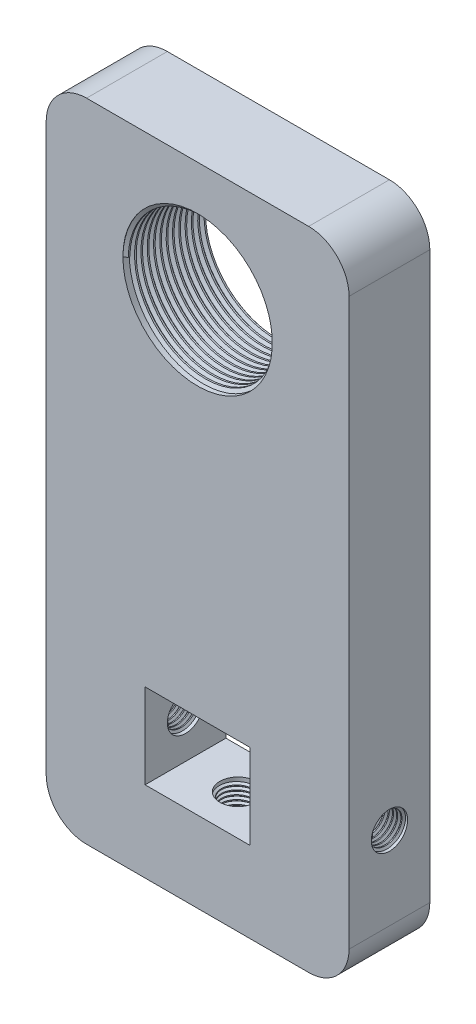
SolidWorks part; units mm, degrees
ref_plane "Front Plane" through (0, 0, 0) normal (0, 0, 1) x (1, 0, 0)
ref_plane "Top Plane" through (0, 0, 0) normal (0, 1, 0) x (1, 0, 0)
ref_plane "Right Plane" through (0, 0, 0) normal (1, 0, 0) x (0, 0, -1)
sketch "Sketch1" plane through (0, 0, 0) normal (0, 0, 1) x (1, 0, 0)
  line L2 (0, 0) -> (0, 66.04)
  line L3 (5.08, 71.12) -> (33.02, 71.12)
  line L4 (38.1, 0) -> (38.1, 66.04)
  line L5 (12.446, 0) -> (12.446, 10.668)
  line L6 (12.446, 10.668) -> (25.654, 10.668)
  line L7 (25.654, 10.668) -> (25.654, 0)
  line L11 (0, 0) -> (0, -5.08)
  line L12 (5.08, -10.16) -> (33.02, -10.16)
  line L13 (38.1, -5.08) -> (38.1, 0)
  line L14 (12.446, 0) -> (25.654, 0)
  line L15 (19.05, 71.12) -> (19.05, 56.134) construction
  line L16 (19.05, 56.134) -> (19.05, 25.654) construction
  line L17 (19.05, 10.668) -> (19.05, 25.654) construction
  line L18 (19.05, 0) -> (19.05, -10.16) construction
  line L19 (0, 10.668) -> (38.1, 10.668) construction
  arc A3 (0, -5.08) -> (5.08, -10.16) centre (5.08, -5.08) ccw
  arc A4 (33.02, -10.16) -> (38.1, -5.08) centre (33.02, -5.08) ccw
  arc A5 (33.02, 71.12) -> (38.1, 66.04) centre (33.02, 66.04) cw
  arc A6 (0, 66.04) -> (5.08, 71.12) centre (5.08, 66.04) cw
  circle A8 centre (19.05, 56.134) radius 9.398
  point P16 (19.05, 71.12)
  point P27 (0, 71.12)
  dimension "D5" = 18.796
  dimension "D7" = 5.08
  dimension "D1" = 13.208
  dimension "D2" = 71.12
  dimension "D3" = 10.668
  dimension "D4" = 10.16
  dimension "D8" = 38.1
extrude "Boss-Extrude2" add sketch "Sketch1" along normal blind 10.16
sketch "Sketch4" plane through (0, 0, 0) normal (-1, 0, 0) x (0, 0, 1)
  circle A0 centre (5.08, 5.334) radius 2.286
  dimension "D1" = 4.572
  dimension "D2" = 5.334
extrude "Cut-Extrude1" cut sketch "Sketch4" against normal blind 38.1
sketch "Sketch6" plane through (0, -10.16, 0) normal (0, -1, 0) x (1, 0, 0)
  line L0 (19.05, 5.08) -> (19.05, 10.16) construction
  line L1 (5.08, 10.16) -> (33.02, 10.16) construction
  line L2 (19.05, 5.08) -> (33.02, 5.08) construction
  line L3 (33.02, 10.16) -> (33.02, 0) construction
  circle A0 centre (19.05, 5.08) radius 2.286
  dimension "D1" = 4.572
extrude "Cut-Extrude2" cut sketch "Sketch6" against normal blind 10.16
thread "Thread1" pitch 0.7937 method extrude profile "Thread Profile1" start angle 0, offset 0, length 9.652, pitch 0.7937, diameter 18.796
ref_plane "Plane1" through (9.652, 56.134, 10.16) normal (0, -1, 0) x (-1, 0, 0)
sketch "Thread Profile1" plane through (9.652, 56.134, 10.16) normal (0, -1, 0) x (-1, 0, 0)
  line L0 (0, 0) -> (0, 0.7937) construction
  line L11 (0, 0) -> (0, 0.6945)
  line L12 (0, 0.6945) -> (-0.4296, 0.4465)
  line L13 (-0.4296, 0.4465) -> (-0.4296, 0.248)
  line L15 (-0.4296, 0.248) -> (0, 0)
  line L17 (-0.4296, 0.3473) -> (0, 0.3473) construction
  point P2 (0, 0)
  dimension "Pitch" = 0.7937
  dimension "Profile_Angle" = 60
  dimension "Profile_Land" = 0.1984
  dimension "Profile_Height" = 0.4296
thread "Thread2" pitch 0.5292 method extrude profile "Thread Profile2" start angle 0, offset 0, length 11.938, pitch 0.5292, diameter 4.572
ref_plane "Plane2" through (0, 5.334, 2.794) normal (0, -1, 0) x (0, 0, -1)
sketch "Thread Profile2" plane through (0, 5.334, 2.794) normal (0, -1, 0) x (0, 0, -1)
  line L0 (0, 0) -> (0, 0.5292) construction
  line L11 (0, 0) -> (0, 0.463)
  line L12 (0, 0.463) -> (-0.2864, 0.2977)
  line L13 (-0.2864, 0.2977) -> (-0.2864, 0.1654)
  line L15 (-0.2864, 0.1654) -> (0, 0)
  line L17 (-0.2864, 0.2315) -> (0, 0.2315) construction
  point P2 (0, 0)
  dimension "Pitch" = 0.5292
  dimension "Profile_Angle" = 60
  dimension "Profile_Land" = 0.1323
  dimension "Profile_Height" = 0.2864
thread "Thread3" pitch 0.5292 method extrude profile "Thread Profile3" start angle 0, offset 0, length 11.938, pitch 0.5292, diameter 4.572
ref_plane "Plane3" through (38.1, 5.334, 7.366) normal (0, -1, 0) x (0, 0, 1)
sketch "Thread Profile3" plane through (38.1, 5.334, 7.366) normal (0, -1, 0) x (0, 0, 1)
  line L0 (0, 0) -> (0, 0.5292) construction
  line L11 (0, 0) -> (0, 0.463)
  line L12 (0, 0.463) -> (-0.2864, 0.2977)
  line L13 (-0.2864, 0.2977) -> (-0.2864, 0.1654)
  line L15 (-0.2864, 0.1654) -> (0, 0)
  line L17 (-0.2864, 0.2315) -> (0, 0.2315) construction
  point P2 (0, 0)
  dimension "Pitch" = 0.5292
  dimension "Profile_Angle" = 60
  dimension "Profile_Land" = 0.1323
  dimension "Profile_Height" = 0.2864
thread "Thread4" pitch 0.5292 method extrude profile "Thread Profile4" start angle 0, offset 0, length 9.652, pitch 0.5292, diameter 4.572
ref_plane "Plane4" through (21.336, -10.16, 5.08) normal (0, 0, 1) x (1, 0, 0)
sketch "Thread Profile4" plane through (21.336, -10.16, 5.08) normal (0, 0, 1) x (1, 0, 0)
  line L0 (0, 0) -> (0, 0.5292) construction
  line L11 (0, 0) -> (0, 0.463)
  line L12 (0, 0.463) -> (-0.2864, 0.2977)
  line L13 (-0.2864, 0.2977) -> (-0.2864, 0.1654)
  line L15 (-0.2864, 0.1654) -> (0, 0)
  line L17 (-0.2864, 0.2315) -> (0, 0.2315) construction
  point P2 (0, 0)
  dimension "Pitch" = 0.5292
  dimension "Profile_Angle" = 60
  dimension "Profile_Land" = 0.1323
  dimension "Profile_Height" = 0.2864
